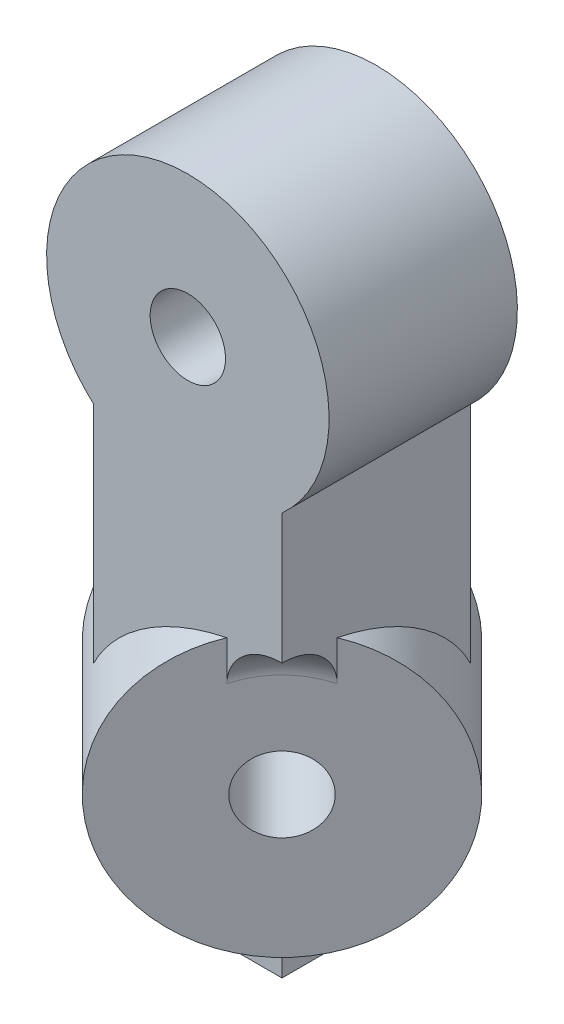
SolidWorks part; units mm, degrees
material "PLA"
ref_plane "Front Plane" through (0, 0, 0) normal (0, 0, 1) x (1, 0, 0)
ref_plane "Top Plane" through (0, 0, 0) normal (0, 1, 0) x (1, 0, 0)
ref_plane "Right Plane" through (0, 0, 0) normal (1, 0, 0) x (0, 0, -1)
sketch "Sketch1" plane through (0, 0, 0) normal (0, 0, 1) x (1, 0, 0)
  line L1 (5.0265, -10.0235) -> (-4.9735, -10.0235)
  line L2 (5.0265, -10.0235) -> (5.0265, 4.3863)
  line L4 (-4.9735, -10.0235) -> (-4.9735, 4.3863)
  line L5 (5.0265, -10.0235) -> (-1.3013, 2.5949) construction
  line L6 (1.288, 2.5958) -> (-4.9735, -10.0235) construction
  arc A0 (5.0265, 4.3863) -> (-4.9735, 4.3863) centre (0.0265, 9.9765) ccw
  circle A1 centre (0.0265, 9.9765) radius 2
  point P0 (0, 0)
  dimension "D2" = 15
  dimension "D3" = 4
  dimension "D1" = 10
  dimension "D4" = 20
extrude "Boss-Extrude1" add sketch "Sketch1" along normal blind 10
ref_plane "Plane1" through (2.5132, 0, 2.5132) normal (-0.7071, 0, -0.7071) x (-0.7071, 0, 0.7071)
sketch "Sketch6" plane through (2.5132, 0, 2.5132) normal (-0.7071, 0, -0.7071) x (-0.7071, 0, 0.7071)
  circle A0 centre (3.5168, -10.0235) radius 7.5
  dimension "D1" = 15
extrude "Boss-Extrude3" add sketch "Sketch6" along normal mid plane 10
sketch "Sketch7" plane through (-1.0223, 0, -1.0223) normal (-0.7071, 0, -0.7071) x (-0.7071, 0, 0.7071)
  line L0 (1.4458, -10.0235) -> (5.5879, -10.0235) construction
  circle A0 centre (3.5168, -10.0235) radius 2
  dimension "D1" = 4
extrude "Cut-Extrude4" cut sketch "Sketch7" against normal through all both and the other way through all
sketch "Sketch10" plane through (6.0488, 0, 6.0488) normal (0.7071, 0, 0.7071) x (0.7071, 0, -0.7071)
  circle A0 centre (-3.5168, -10.0235) radius 7.5
extrude "Cut-Extrude7" cut sketch "Sketch10" along normal blind 9
mirror "Mirror1" about plane through (2.5132, 0, 2.5132) normal (-0.7071, 0, -0.7071) of "Cut-Extrude7"
ref_plane "Plane2" through (0, -17.5, 0) normal (0, 1, 0) x (1, 0, 0)
sketch "Sketch11" plane through (0, -17.5, 0) normal (0, 1, 0) x (1, 0, 0)
  line L0 (-5.2768, -10.3033) -> (5.3298, 0.3033) construction
  line L1 (-8.8124, -6.7678) -> (-1.7413, -13.8388) construction
  line L2 (8.8653, -3.2322) -> (1.7942, 3.8388) construction
  line L4 (2.0265, -3) -> (-1.9735, -3)
  line L5 (2.0265, -3) -> (2.0265, -7)
  line L6 (2.0265, -7) -> (-1.9735, -7)
  line L7 (-1.9735, -3) -> (-1.9735, -7)
  line L8 (2.0265, -3) -> (-1.9735, -7) construction
  line L9 (2.0265, -7) -> (-1.9735, -3) construction
  point P6 (0.0265, -5)
  dimension "D1" = 4
extrude "Boss-Extrude4" add sketch "Sketch11" along normal mid plane 5
fillet "Fillet1" radius 2 2 edges at (3.562, -2.5235, 8.5355) (-3.5091, -2.5235, 1.4645)
sketch "Sketch12" plane through (0, 0, 3) normal (0, 0, -1) x (-1, 0, 0)
  line L0 (-0.0265, -20) -> (-0.0265, -18) construction
  line L1 (-2.0265, -20) -> (1.9735, -20) construction
  circle A0 centre (-0.0265, -18) radius 0.5
  dimension "D2" = 1
  dimension "D1" = 2
extrude "Cut-Extrude8" cut sketch "Sketch12" against normal blind 10
